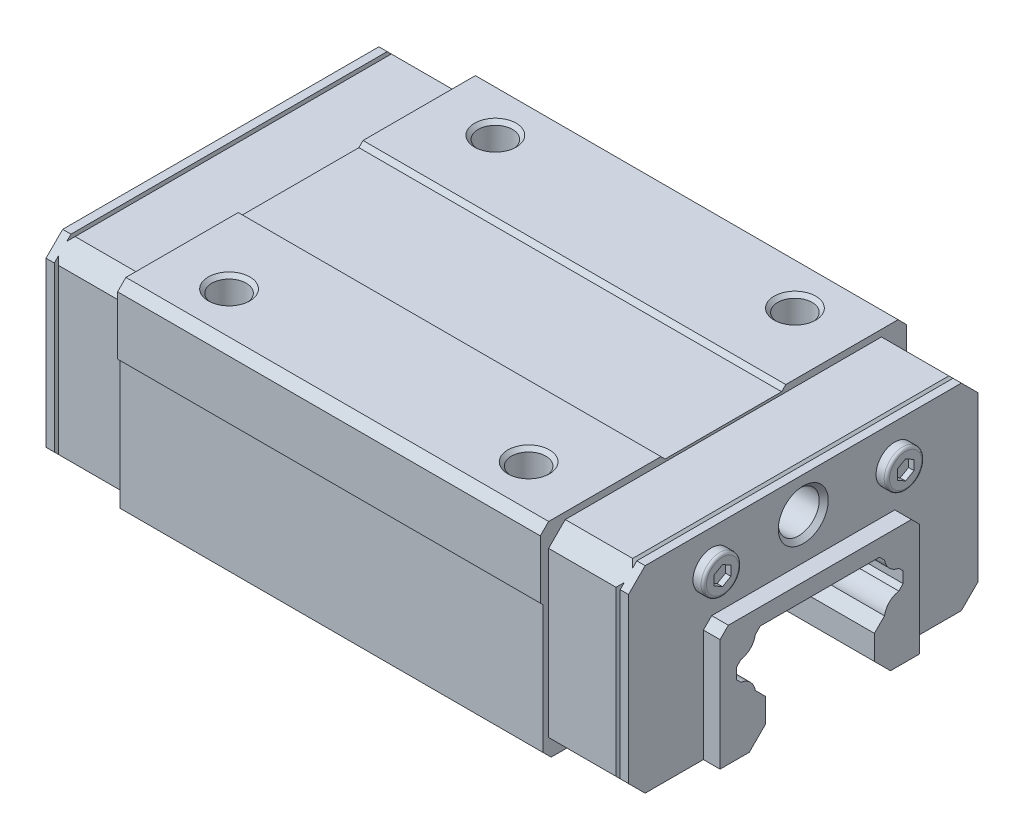
SolidWorks part; units mm, degrees
ref_plane "Front Plane" through (0, 0, 0) normal (0, 0, 1) x (1, 0, 0)
ref_plane "Top Plane" through (0, 0, 0) normal (0, 1, 0) x (1, 0, 0)
ref_plane "Right Plane" through (0, 0, 0) normal (1, 0, 0) x (0, 0, -1)
ref_plane "Plane1" through (0, 0, 0) normal (1, 0, 0) x (0, 0, -1)
sketch "Sketch1" plane through (0, 0, 0) normal (1, 0, 0) x (0, 0, -1)
  line L0 (-22, 18) -> (-21.7, 17.7)
  line L1 (-21.7, 17.7) -> (-21.7, 2.317)
  line L2 (-21.7, 2.317) -> (-20.7, 1.317)
  line L3 (-20.7, 1.317) -> (-16.3, 1.317)
  line L4 (-16.3, 1.317) -> (-16.3, 1.587)
  line L5 (-16.3, 1.587) -> (16.3, 1.587)
  line L6 (16.3, 1.587) -> (16.3, 1.317)
  line L7 (16.3, 1.317) -> (20.7, 1.317)
  line L8 (20.7, 1.317) -> (21.7, 2.317)
  line L9 (21.7, 2.317) -> (21.7, 17.7)
  line L10 (21.7, 17.7) -> (22, 18)
  line L11 (22, 18) -> (22, 25)
  line L12 (22, 25) -> (21, 26)
  line L13 (21, 26) -> (7.5, 26)
  line L14 (7.5, 26) -> (7, 25.5)
  line L15 (7, 25.5) -> (-7, 25.5)
  line L16 (-7, 25.5) -> (-7.5, 26)
  line L17 (-7.5, 26) -> (-21, 26)
  line L18 (-21, 26) -> (-22, 25)
  line L19 (-22, 25) -> (-22, 18)
extrude "Boss-Extrude1" add sketch "Sketch1" against normal blind 25.4 and the other way blind 25.4
ref_plane "Plane2" through (0, 0, 16) normal (0, 0, 1) x (1, 0, 0)
sketch "Sketch2" plane through (0, 0, 16) normal (0, 0, 1) x (1, 0, 0)
  line L0 (-18, 17.6066) -> (-20.067, 18.8)
  line L1 (-20.067, 18.8) -> (-20.067, 25.567)
  line L2 (-20.067, 25.567) -> (-20.5, 26)
  line L3 (-20.5, 26) -> (-18, 26)
  line L4 (-18, 26) -> (-18, 17.6066)
  line L5 (-18, 26) -> (-18, 17.6066) construction
revolve "Cut-Revolve1" cut sketch "Sketch2" angle 360 about L5 reverse direction yes
ref_plane "Plane3" through (0, 0, -16) normal (0, 0, 1) x (1, 0, 0)
sketch "Sketch3" plane through (0, 0, -16) normal (0, 0, 1) x (1, 0, 0)
  line L0 (-18, 17.6066) -> (-20.067, 18.8)
  line L1 (-20.067, 18.8) -> (-20.067, 25.567)
  line L2 (-20.067, 25.567) -> (-20.5, 26)
  line L3 (-20.5, 26) -> (-18, 26)
  line L4 (-18, 26) -> (-18, 17.6066)
  line L5 (-18, 26) -> (-18, 17.6066) construction
revolve "Cut-Revolve2" cut sketch "Sketch3" angle 360 about L5 reverse direction yes
ref_plane "Plane4" through (0, 0, -16) normal (0, 0, 1) x (1, 0, 0)
sketch "Sketch4" plane through (0, 0, -16) normal (0, 0, 1) x (1, 0, 0)
  line L0 (18, 17.6066) -> (15.933, 18.8)
  line L1 (15.933, 18.8) -> (15.933, 25.567)
  line L2 (15.933, 25.567) -> (15.5, 26)
  line L3 (15.5, 26) -> (18, 26)
  line L4 (18, 26) -> (18, 17.6066)
  line L5 (18, 26) -> (18, 17.6066) construction
revolve "Cut-Revolve3" cut sketch "Sketch4" angle 360 about L5 reverse direction yes
ref_plane "Plane5" through (0, 0, 16) normal (0, 0, 1) x (1, 0, 0)
sketch "Sketch5" plane through (0, 0, 16) normal (0, 0, 1) x (1, 0, 0)
  line L0 (18, 17.6066) -> (15.933, 18.8)
  line L1 (15.933, 18.8) -> (15.933, 25.567)
  line L2 (15.933, 25.567) -> (15.5, 26)
  line L3 (15.5, 26) -> (18, 26)
  line L4 (18, 26) -> (18, 17.6066)
  line L5 (18, 26) -> (18, 17.6066) construction
revolve "Cut-Revolve4" cut sketch "Sketch5" angle 360 about L5 reverse direction yes
ref_plane "Plane6" through (-34, 0, 0) normal (1, 0, 0) x (0, 0, -1)
sketch "Sketch6" plane through (-34, 0, 0) normal (1, 0, 0) x (0, 0, -1)
  line L0 (-21, 23.2) -> (-21, 3.517)
  line L1 (-21, 3.517) -> (-19, 1.517)
  line L2 (-19, 1.517) -> (19, 1.517)
  line L3 (19, 1.517) -> (21, 3.517)
  line L4 (21, 3.517) -> (21, 23.2)
  line L5 (21, 23.2) -> (19, 25.2)
  line L6 (19, 25.2) -> (-19, 25.2)
  line L7 (-19, 25.2) -> (-21, 23.2)
extrude "Boss-Extrude2" add sketch "Sketch6" along normal blind 8.6
ref_plane "Plane7" through (-34, 0, 0) normal (1, 0, 0) x (0, 0, -1)
sketch "Sketch7" plane through (-34, 0, 0) normal (1, 0, 0) x (0, 0, -1)
  line L0 (-21, 23.2) -> (-21, 3.517)
  line L1 (-21, 3.517) -> (-19, 1.517)
  line L2 (-19, 1.517) -> (19, 1.517)
  line L3 (19, 1.517) -> (21, 3.517)
  line L4 (21, 3.517) -> (21, 23.2)
  line L5 (21, 23.2) -> (19, 25.2)
  line L6 (19, 25.2) -> (-19, 25.2)
  line L7 (-19, 25.2) -> (-21, 23.2)
extrude "Boss-Extrude3" add sketch "Sketch7" against normal blind 3
ref_plane "Plane8" through (34, 0, 0) normal (1, 0, 0) x (0, 0, -1)
sketch "Sketch8" plane through (34, 0, 0) normal (1, 0, 0) x (0, 0, -1)
  line L0 (-21, 23.2) -> (-21, 3.517)
  line L1 (-21, 3.517) -> (-19, 1.517)
  line L2 (-19, 1.517) -> (19, 1.517)
  line L3 (19, 1.517) -> (21, 3.517)
  line L4 (21, 3.517) -> (21, 23.2)
  line L5 (21, 23.2) -> (19, 25.2)
  line L6 (19, 25.2) -> (-19, 25.2)
  line L7 (-19, 25.2) -> (-21, 23.2)
extrude "Boss-Extrude4" add sketch "Sketch8" against normal blind 8.6
ref_plane "Plane9" through (34, 0, 0) normal (1, 0, 0) x (0, 0, -1)
sketch "Sketch9" plane through (34, 0, 0) normal (1, 0, 0) x (0, 0, -1)
  line L0 (-21, 23.2) -> (-21, 3.517)
  line L1 (-21, 3.517) -> (-19, 1.517)
  line L2 (-19, 1.517) -> (19, 1.517)
  line L3 (19, 1.517) -> (21, 3.517)
  line L4 (21, 3.517) -> (21, 23.2)
  line L5 (21, 23.2) -> (19, 25.2)
  line L6 (19, 25.2) -> (-19, 25.2)
  line L7 (-19, 25.2) -> (-21, 23.2)
extrude "Boss-Extrude5" add sketch "Sketch9" along normal blind 3
ref_plane "Plane10" through (37, 0, 0) normal (1, 0, 0) x (0, 0, -1)
sketch "Sketch10" plane through (37, 0, 0) normal (1, 0, 0) x (0, 0, -1)
  line L0 (-21, 0) -> (21, 0)
  line L1 (21, 0) -> (21, 26)
  line L2 (21, 26) -> (-21, 26)
  line L3 (-21, 26) -> (-21, 0)
extrude "Cut-Extrude1" cut sketch "Sketch10" against normal blind 2
ref_plane "Plane11" through (-37, 0, 0) normal (1, 0, 0) x (0, 0, -1)
sketch "Sketch11" plane through (-37, 0, 0) normal (1, 0, 0) x (0, 0, -1)
  line L0 (-21, 0) -> (21, 0)
  line L1 (21, 0) -> (21, 26)
  line L2 (21, 26) -> (-21, 26)
  line L3 (-21, 26) -> (-21, 0)
extrude "Cut-Extrude2" cut sketch "Sketch11" along normal blind 2
ref_plane "Plane12" through (-35, 0, 0) normal (1, 0, 0) x (0, 0, -1)
sketch "Sketch12" plane through (-35, 0, 0) normal (1, 0, 0) x (0, 0, -1)
  line L0 (-12, 15) -> (-12, 1.517)
  line L1 (-12, 1.517) -> (12, 1.517)
  line L2 (12, 1.517) -> (12, 15)
  line L3 (12, 15) -> (11, 16)
  line L4 (11, 16) -> (-11, 16)
  line L5 (-11, 16) -> (-12, 15)
extrude "Boss-Extrude6" add sketch "Sketch12" against normal blind 2
ref_plane "Plane13" through (35, 0, 0) normal (1, 0, 0) x (0, 0, -1)
sketch "Sketch13" plane through (35, 0, 0) normal (1, 0, 0) x (0, 0, -1)
  line L0 (-12, 15) -> (-12, 1.517)
  line L1 (-12, 1.517) -> (12, 1.517)
  line L2 (12, 1.517) -> (12, 15)
  line L3 (12, 15) -> (11, 16)
  line L4 (11, 16) -> (-11, 16)
  line L5 (-11, 16) -> (-12, 15)
extrude "Boss-Extrude7" add sketch "Sketch13" along normal blind 2
ref_plane "Plane14" through (0, 0, 0) normal (1, 0, 0) x (0, 0, -1)
sketch "Sketch14" plane through (0, 0, 0) normal (1, 0, 0) x (0, 0, -1)
  line L0 (-10, -3.5) -> (10, -3.5)
  line L1 (10, -3.5) -> (10, 0.0001)
  line L2 (10, 0.0001) -> (6.55, 3.45)
  line L3 (6.55, 3.45) -> (6.55, 6.3792)
  line L4 (6.55, 6.3792) -> (7.7659, 7.5951)
  line L5 (9.4852, 9.3144) -> (10, 9.8292)
  line L6 (10, 9.8292) -> (10, 11.16)
  line L7 (10, 11.16) -> (9.4727, 11.6874)
  line L8 (7.7679, 13.3921) -> (7.16, 14)
  line L9 (7.16, 14) -> (-7.16, 14)
  line L10 (-7.16, 14) -> (-7.7679, 13.3921)
  line L11 (-9.4727, 11.6874) -> (-10, 11.16)
  line L12 (-10, 11.16) -> (-10, 9.8292)
  line L13 (-10, 9.8292) -> (-9.4852, 9.3144)
  line L14 (-7.7659, 7.5951) -> (-6.55, 6.3792)
  line L15 (-6.55, 6.3792) -> (-6.55, 3.45)
  line L16 (-6.55, 3.45) -> (-10, 0.0001)
  line L17 (-10, 0.0001) -> (-10, -3.5)
  arc A0 (7.7659, 7.5951) -> (9.4852, 9.3144) centre (9.8015, 7.2788) cw
  arc A1 (9.4727, 11.6874) -> (7.7679, 13.3921) centre (9.8015, 13.7209) cw
  arc A2 (-7.7679, 13.3921) -> (-9.4727, 11.6874) centre (-9.8015, 13.7209) cw
  arc A3 (-9.4852, 9.3144) -> (-7.7659, 7.5951) centre (-9.8015, 7.2788) cw
extrude "Cut-Extrude3" cut sketch "Sketch14" against normal blind 37 and the other way blind 37
ref_plane "Plane15" through (0, 0, -11) normal (0, 0, 1) x (1, 0, 0)
sketch "Sketch15" plane through (0, 0, -11) normal (0, 0, 1) x (1, 0, 0)
  line L0 (35, 20.817) -> (35, 23.067)
  line L1 (35, 23.067) -> (35.975, 23.067)
  line L2 (36.3, 22.742) -> (36.3, 20.817)
  line L3 (36.3, 20.817) -> (35, 20.817)
  line L4 (36.3, 20.817) -> (35, 20.817) construction
  arc A0 (35.975, 23.067) -> (36.3, 22.742) centre (35.975, 22.742) cw
revolve "Revolve1" add sketch "Sketch15" angle 360 about L4 reverse direction yes
ref_plane "Plane16" through (0, 0, -11) normal (0, 0, 1) x (1, 0, 0)
sketch "Sketch16" plane through (0, 0, -11) normal (0, 0, 1) x (1, 0, 0)
  line L0 (-36.3, 20.817) -> (-36.3, 22.742)
  line L1 (-35.975, 23.067) -> (-35, 23.067)
  line L2 (-35, 23.067) -> (-35, 20.817)
  line L3 (-35, 20.817) -> (-36.3, 20.817)
  line L4 (-35, 20.817) -> (-36.3, 20.817) construction
  arc A0 (-36.3, 22.742) -> (-35.975, 23.067) centre (-35.975, 22.742) cw
revolve "Revolve2" add sketch "Sketch16" angle 360 about L4 reverse direction yes
ref_plane "Plane17" through (0, 0, 11) normal (0, 0, 1) x (1, 0, 0)
sketch "Sketch17" plane through (0, 0, 11) normal (0, 0, 1) x (1, 0, 0)
  line L0 (35, 20.817) -> (35, 23.067)
  line L1 (35, 23.067) -> (35.975, 23.067)
  line L2 (36.3, 22.742) -> (36.3, 20.817)
  line L3 (36.3, 20.817) -> (35, 20.817)
  line L4 (36.3, 20.817) -> (35, 20.817) construction
  arc A0 (35.975, 23.067) -> (36.3, 22.742) centre (35.975, 22.742) cw
revolve "Revolve3" add sketch "Sketch17" angle 360 about L4 reverse direction yes
ref_plane "Plane18" through (0, 0, 11) normal (0, 0, 1) x (1, 0, 0)
sketch "Sketch18" plane through (0, 0, 11) normal (0, 0, 1) x (1, 0, 0)
  line L0 (-36.3, 20.817) -> (-36.3, 22.742)
  line L1 (-35.975, 23.067) -> (-35, 23.067)
  line L2 (-35, 23.067) -> (-35, 20.817)
  line L3 (-35, 20.817) -> (-36.3, 20.817)
  line L4 (-35, 20.817) -> (-36.3, 20.817) construction
  arc A0 (-36.3, 22.742) -> (-35.975, 23.067) centre (-35.975, 22.742) cw
revolve "Revolve4" add sketch "Sketch18" angle 360 about L4 reverse direction yes
ref_plane "Plane19" through (36.3, 0, 0) normal (1, 0, 0) x (0, 0, -1)
sketch "Sketch19" plane through (36.3, 0, 0) normal (1, 0, 0) x (0, 0, -1)
  line L0 (10, 21.3944) -> (10, 20.2396)
  line L1 (10, 20.2396) -> (11, 19.6623)
  line L2 (11, 19.6623) -> (12, 20.2396)
  line L3 (12, 20.2396) -> (12, 21.3944)
  line L4 (12, 21.3944) -> (11, 21.9717)
  line L5 (11, 21.9717) -> (10, 21.3944)
extrude "Cut-Extrude4" cut sketch "Sketch19" against normal blind 0.65
ref_plane "Plane20" through (36.3, 0, 0) normal (1, 0, 0) x (0, 0, -1)
sketch "Sketch20" plane through (36.3, 0, 0) normal (1, 0, 0) x (0, 0, -1)
  line L0 (-12, 21.3944) -> (-12, 20.2396)
  line L1 (-12, 20.2396) -> (-11, 19.6623)
  line L2 (-11, 19.6623) -> (-10, 20.2396)
  line L3 (-10, 20.2396) -> (-10, 21.3944)
  line L4 (-10, 21.3944) -> (-11, 21.9717)
  line L5 (-11, 21.9717) -> (-12, 21.3944)
extrude "Cut-Extrude5" cut sketch "Sketch20" against normal blind 0.65
ref_plane "Plane21" through (-36.3, 0, 0) normal (1, 0, 0) x (0, 0, -1)
sketch "Sketch21" plane through (-36.3, 0, 0) normal (1, 0, 0) x (0, 0, -1)
  line L0 (10, 21.3944) -> (10, 20.2396)
  line L1 (10, 20.2396) -> (11, 19.6623)
  line L2 (11, 19.6623) -> (12, 20.2396)
  line L3 (12, 20.2396) -> (12, 21.3944)
  line L4 (12, 21.3944) -> (11, 21.9717)
  line L5 (11, 21.9717) -> (10, 21.3944)
extrude "Cut-Extrude6" cut sketch "Sketch21" along normal blind 0.65
ref_plane "Plane22" through (-36.3, 0, 0) normal (1, 0, 0) x (0, 0, -1)
sketch "Sketch22" plane through (-36.3, 0, 0) normal (1, 0, 0) x (0, 0, -1)
  line L0 (-12, 21.3944) -> (-12, 20.2396)
  line L1 (-12, 20.2396) -> (-11, 19.6623)
  line L2 (-11, 19.6623) -> (-10, 20.2396)
  line L3 (-10, 20.2396) -> (-10, 21.3944)
  line L4 (-10, 21.3944) -> (-11, 21.9717)
  line L5 (-11, 21.9717) -> (-12, 21.3944)
extrude "Cut-Extrude7" cut sketch "Sketch22" along normal blind 0.65
ref_plane "Plane23" through (0, 0, 0) normal (0, 0, 1) x (1, 0, 0)
sketch "Sketch23" plane through (0, 0, 0) normal (0, 0, 1) x (1, 0, 0)
  line L0 (-34, 25.2) -> (-34, 24.7)
  line L1 (-34, 24.7) -> (-33.5, 25.2)
  line L2 (-33.5, 25.2) -> (-34, 25.2)
extrude "Cut-Extrude8" cut sketch "Sketch23" against normal blind 21 and the other way blind 21
ref_plane "Plane24" through (0, 0, 0) normal (0, 0, 1) x (1, 0, 0)
sketch "Sketch24" plane through (0, 0, 0) normal (0, 0, 1) x (1, 0, 0)
  line L0 (33.5, 25.2) -> (34, 24.7)
  line L1 (34, 24.7) -> (34, 25.2)
  line L2 (34, 25.2) -> (33.5, 25.2)
extrude "Cut-Extrude9" cut sketch "Sketch24" against normal blind 21 and the other way blind 21
ref_plane "Plane25" through (0, 0, 0) normal (0, 1, 0) x (1, 0, 0)
sketch "Sketch25" plane through (0, 0, 0) normal (0, 1, 0) x (1, 0, 0)
  line L0 (33.5, 21) -> (34, 20.5)
  line L1 (34, 20.5) -> (34, 21)
  line L2 (34, 21) -> (33.5, 21)
extrude "Cut-Extrude10" cut sketch "Sketch25" along normal blind 26
ref_plane "Plane26" through (0, 0, 0) normal (0, 1, 0) x (1, 0, 0)
sketch "Sketch26" plane through (0, 0, 0) normal (0, 1, 0) x (1, 0, 0)
  line L0 (-34, 21) -> (-34, 20.5)
  line L1 (-34, 20.5) -> (-33.5, 21)
  line L2 (-33.5, 21) -> (-34, 21)
extrude "Cut-Extrude11" cut sketch "Sketch26" along normal blind 26
ref_plane "Plane27" through (0, 0, 0) normal (0, 1, 0) x (1, 0, 0)
sketch "Sketch27" plane through (0, 0, 0) normal (0, 1, 0) x (1, 0, 0)
  line L0 (33.5, -21) -> (34, -21)
  line L1 (34, -21) -> (34, -20.5)
  line L2 (34, -20.5) -> (33.5, -21)
extrude "Cut-Extrude12" cut sketch "Sketch27" along normal blind 26
ref_plane "Plane28" through (0, 0, 0) normal (0, 1, 0) x (1, 0, 0)
sketch "Sketch28" plane through (0, 0, 0) normal (0, 1, 0) x (1, 0, 0)
  line L0 (-34, -21) -> (-33.5, -21)
  line L1 (-33.5, -21) -> (-34, -20.5)
  line L2 (-34, -20.5) -> (-34, -21)
extrude "Cut-Extrude13" cut sketch "Sketch28" along normal blind 26
ref_plane "Plane29" through (0, 0, 0) normal (0, 0, 1) x (1, 0, 0)
sketch "Sketch29" plane through (0, 0, 0) normal (0, 0, 1) x (1, 0, 0)
  line L0 (27.5806, 21) -> (29, 23.4585)
  line L1 (29, 23.4585) -> (34.4585, 23.4585)
  line L2 (34.4585, 23.4585) -> (35, 24)
  line L3 (35, 24) -> (35, 21)
  line L4 (35, 21) -> (27.5806, 21)
  line L5 (35, 21) -> (27.5806, 21) construction
revolve "Cut-Revolve5" cut sketch "Sketch29" angle 360 about L5 reverse direction yes
ref_plane "Plane30" through (0, 0, 0) normal (0, 0, 1) x (1, 0, 0)
sketch "Sketch30" plane through (0, 0, 0) normal (0, 0, 1) x (1, 0, 0)
  line L0 (-35, 21) -> (-35, 24)
  line L1 (-35, 24) -> (-34.4585, 23.4585)
  line L2 (-34.4585, 23.4585) -> (-29, 23.4585)
  line L3 (-29, 23.4585) -> (-27.5806, 21)
  line L4 (-27.5806, 21) -> (-35, 21)
  line L5 (-27.5806, 21) -> (-35, 21) construction
revolve "Cut-Revolve6" cut sketch "Sketch30" angle 360 about L5 reverse direction yes
ref_plane "Plane31" through (0, 0, -13.4) normal (0, 0, 1) x (1, 0, 0)
sketch "Sketch31" plane through (0, 0, -13.4) normal (0, 0, 1) x (1, 0, 0)
  line L0 (-20, 0) -> (-21.372, 0)
  line L1 (-21.715, 0.343) -> (-21.715, 3.43)
  line L2 (-21.715, 3.43) -> (-20, 3.43)
  line L3 (-20, 3.43) -> (-20, 0)
  line L4 (-20, 3.43) -> (-20, 0) construction
  arc A0 (-21.372, 0) -> (-21.715, 0.343) centre (-21.372, 0.343) cw
revolve "Revolve5" add sketch "Sketch31" angle 360 about L4 reverse direction yes
ref_plane "Plane32" through (0, 0, -13.4) normal (0, 0, 1) x (1, 0, 0)
sketch "Sketch32" plane through (0, 0, -13.4) normal (0, 0, 1) x (1, 0, 0)
  line L0 (20, 0) -> (18.628, 0)
  line L1 (18.285, 0.343) -> (18.285, 3.43)
  line L2 (18.285, 3.43) -> (20, 3.43)
  line L3 (20, 3.43) -> (20, 0)
  line L4 (20, 3.43) -> (20, 0) construction
  arc A0 (18.628, 0) -> (18.285, 0.343) centre (18.628, 0.343) cw
revolve "Revolve6" add sketch "Sketch32" angle 360 about L4 reverse direction yes
ref_plane "Plane33" through (0, 0, 13.4) normal (0, 0, 1) x (1, 0, 0)
sketch "Sketch33" plane through (0, 0, 13.4) normal (0, 0, 1) x (1, 0, 0)
  line L0 (-20, 0) -> (-21.372, 0)
  line L1 (-21.715, 0.343) -> (-21.715, 3.43)
  line L2 (-21.715, 3.43) -> (-20, 3.43)
  line L3 (-20, 3.43) -> (-20, 0)
  line L4 (-20, 3.43) -> (-20, 0) construction
  arc A0 (-21.372, 0) -> (-21.715, 0.343) centre (-21.372, 0.343) cw
revolve "Revolve7" add sketch "Sketch33" angle 360 about L4 reverse direction yes
ref_plane "Plane34" through (0, 0, 13.4) normal (0, 0, 1) x (1, 0, 0)
sketch "Sketch34" plane through (0, 0, 13.4) normal (0, 0, 1) x (1, 0, 0)
  line L0 (20, 0) -> (18.628, 0)
  line L1 (18.285, 0.343) -> (18.285, 3.43)
  line L2 (18.285, 3.43) -> (20, 3.43)
  line L3 (20, 3.43) -> (20, 0)
  line L4 (20, 3.43) -> (20, 0) construction
  arc A0 (18.628, 0) -> (18.285, 0.343) centre (18.628, 0.343) cw
revolve "Revolve8" add sketch "Sketch34" angle 360 about L4 reverse direction yes
